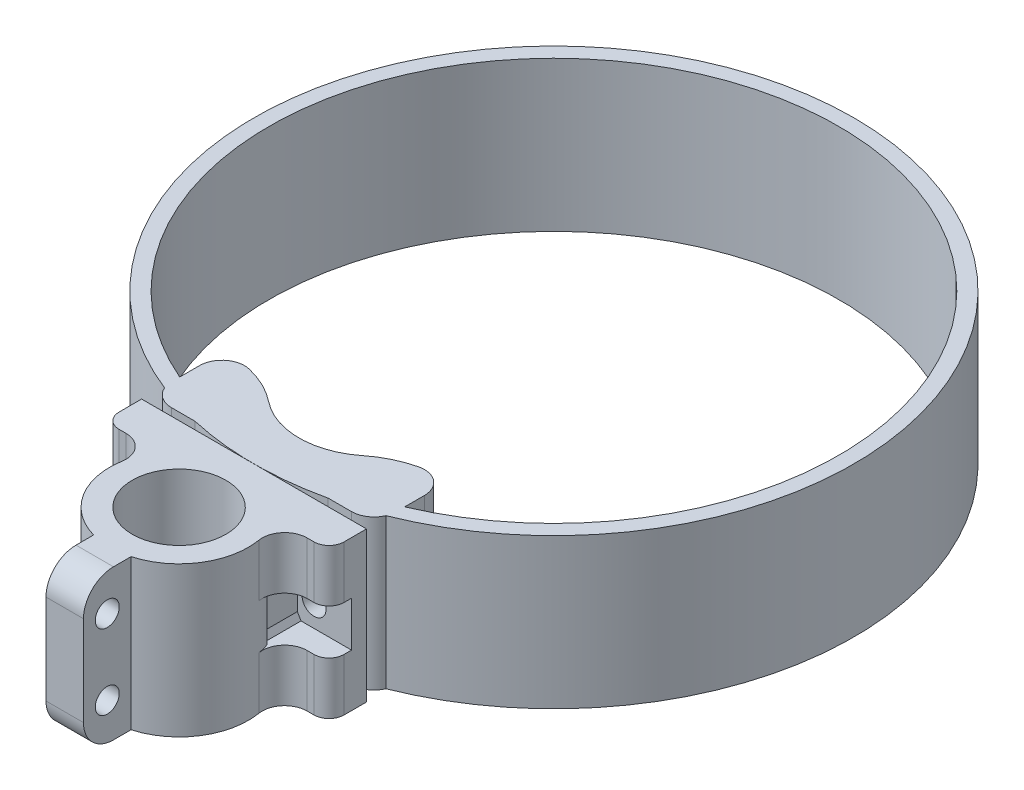
SolidWorks part; units mm, degrees
ref_plane "前视基准面" through (0, 0, 0) normal (0, 0, 1) x (1, 0, 0)
ref_plane "上视基准面" through (0, 0, 0) normal (0, 1, 0) x (1, 0, 0)
ref_plane "右视基准面" through (0, 0, 0) normal (1, 0, 0) x (0, 0, -1)
sketch "草图1" plane through (0, 0, 0) normal (0, 1, 0) x (1, 0, 0)
  circle A0 centre (0, 0) radius 6.25
  circle A1 centre (0, 0) radius 9.25
  dimension "D1" = 12.5
  dimension "D2" = 3
extrude "凸台-拉伸1" add sketch "草图1" along normal blind 20
sketch "草图3" plane through (0, 0, 0) normal (0, -1, 0) x (1, 0, 0)
  line L0 (0, 18.7983) -> (0, -20.8781) construction
  line L1 (-15, -10) -> (15, -10)
  line L2 (15, -10) -> (15, -5)
  line L3 (15, -5) -> (3.75, -5)
  line L4 (-15, -10) -> (-15, -5)
  line L5 (0, -5) -> (-3.75, -5) construction
  line L6 (-3.75, -5) -> (-15, -5)
  line L7 (3.75, -5) -> (0, -5) construction
  circle A0 centre (0, 0) radius 6.25 construction
  arc A1 (-3.75, -5) -> (3.75, -5) centre (0, 0) ccw
  arc A2 (0, 6.25) -> (-3.75, -5) centre (0, 0) ccw construction
  arc A3 (3.75, -5) -> (0, 6.25) centre (0, 0) ccw construction
  point P3 (0, -5)
  point P9 (0, -10)
  dimension "D1" = 30
  dimension "D2" = 5
  dimension "D3" = 10
extrude "凸台-拉伸2" add sketch "草图3" against normal up to surface (20 mm away) up to face at (0, 20, 9.25)
sketch "草图4" plane through (0, 0, -10) normal (0, 0, -1) x (-1, 0, 0)
  line L0 (0, 35.3363) -> (0, -16.1213) construction
  line L1 (-15, 10) -> (15, 10) construction
  line L2 (-15, 20) -> (-15, 0) construction
  line L3 (15, 20) -> (15, 0) construction
  circle A0 centre (-10, 10) radius 1.6
  circle A1 centre (10, 10) radius 1.6
  dimension "D1" = 3.2
  dimension "D2" = 20
extrude "切除-拉伸1" cut sketch "草图4" against normal up to next
ref_plane "基准面1" through (0, 0, 20) normal (0, 0, 1) x (1, 0, 0)
sketch "草图6" plane through (0, 0, 20) normal (0, 0, 1) x (1, 0, 0)
  line L0 (0, 0) -> (0, 19.0192) construction
  line L1 (-10, 13.4641) -> (-13, 11.7321)
  line L2 (-13, 11.7321) -> (-13, 8.2679)
  line L3 (-13, 8.2679) -> (-10, 6.5359)
  line L4 (-10, 6.5359) -> (-7, 8.2679)
  line L5 (-7, 8.2679) -> (-7, 11.7321)
  line L6 (-7, 11.7321) -> (-10, 13.4641)
  line L7 (7, 11.7321) -> (10, 13.4641)
  line L8 (7, 8.2679) -> (7, 11.7321)
  line L9 (10, 6.5359) -> (7, 8.2679)
  line L10 (13, 8.2679) -> (10, 6.5359)
  line L11 (13, 11.7321) -> (13, 8.2679)
  line L12 (10, 13.4641) -> (13, 11.7321)
  circle A2 centre (-10, 10) radius 3 construction
  dimension "D1" = 6
sketch "草图7" plane through (0, 0, -5) normal (0, 0, 1) x (1, 0, 0)
  line L0 (-11.7321, 13) -> (-15, 13)
  line L1 (-6.5359, 10) -> (-8.2679, 13)
  line L2 (-8.2679, 13) -> (-11.7321, 13)
  line L3 (-11.7321, 13) -> (-13.4641, 10)
  line L4 (-13.4641, 10) -> (-11.7321, 7)
  line L5 (-11.7321, 7) -> (-8.2679, 7)
  line L6 (-8.2679, 7) -> (-6.5359, 10)
  line L7 (-15, 20) -> (-15, 0) construction
  line L8 (-15, 13) -> (-15, 7)
  line L9 (-15, 7) -> (-11.7321, 7)
  line L10 (0, -2.9099) -> (0, 23.8281) construction
  line L11 (11.7321, 13) -> (15, 13)
  line L12 (15, 7) -> (11.7321, 7)
  line L13 (15, 13) -> (15, 7)
  line L14 (8.2679, 7) -> (6.5359, 10)
  line L15 (11.7321, 7) -> (8.2679, 7)
  line L16 (13.4641, 10) -> (11.7321, 7)
  line L17 (11.7321, 13) -> (13.4641, 10)
  line L18 (8.2679, 13) -> (11.7321, 13)
  line L19 (6.5359, 10) -> (8.2679, 13)
  circle A0 centre (-10, 10) radius 3 construction
  dimension "D1" = 6
extrude "切除-拉伸5" cut sketch "草图7" against normal blind 3
sketch "草图9" plane through (0, 0, 0) normal (0, 1, 0) x (1, 0, 0)
  line L0 (0, 2.9381) -> (0, -13.8692) construction
  line L2 (-2.5, -15.25) -> (2.5, -15.25)
  line L3 (-2.5, -15.25) -> (-2.5, -8.25)
  line L4 (-2.5, -8.25) -> (2.5, -8.25)
  line L5 (2.5, -15.25) -> (2.5, -8.25)
  line L6 (-2.5, -15.25) -> (2.5, -8.25) construction
  line L7 (-2.5, -8.25) -> (2.5, -15.25) construction
  arc A2 (-7.7822, 5) -> (7.7822, 5) centre (0, 0) ccw construction
  point P3 (0, -11.75)
  dimension "D3" = 6
  dimension "D1" = 7
  dimension "D2" = 5
extrude "凸台-拉伸3" add sketch "草图9" along normal up to surface (20 mm away) up to face at (0, 20, -4.2917)
sketch "草图10" plane through (-2.5, 0, 0) normal (-1, 0, 0) x (0, 0, 1)
  line L0 (12.0779, 20) -> (12.0779, 0) construction
  line L1 (8.9058, 20) -> (15.25, 20) construction
  line L2 (8.9058, 0) -> (15.25, 0) construction
  line L3 (15.25, 10) -> (5.2269, 10) construction
  line L4 (15.25, 20) -> (15.25, 0) construction
  circle A0 centre (12.0779, 15) radius 1.6
  circle A1 centre (12.0779, 5) radius 1.6
  dimension "D1" = 3.2
  dimension "D2" = 10
extrude "切除-拉伸7" cut sketch "草图10" against normal up to next
fillet "圆角1" radius 4 2 edges at (0, 0, 15.25) (0, 20, 15.25)
sketch "草图11" plane through (0, 0, 0) normal (0, -1, 0) x (1, 0, 0)
  line L0 (15, -5) -> (7.7822, -5) construction
  line L1 (12.0856, -5) -> (7.7822, -5)
  line L2 (0, 4.128) -> (0, -10.8528) construction
  line L3 (-12.0856, -5) -> (-7.7822, -5)
  arc A0 (7.7822, -5) -> (2.5, 8.9058) centre (0, 0) ccw construction
  arc A1 (7.7822, -5) -> (9.1259, -1.5102) centre (0, 0) ccw
  arc A2 (9.1259, -1.5102) -> (12.0856, -5) centre (12.0856, -2) ccw
  arc A3 (-9.1259, -1.5102) -> (-12.0856, -5) centre (-12.0856, -2) cw
  arc A4 (-7.7822, -5) -> (-9.1259, -1.5102) centre (0, 0) cw
  dimension "D1" = 6
extrude "凸台-拉伸4" add sketch "草图11" against normal blind 7
ref_plane "基准面2" through (0, 10, 0) normal (0, 1, 0) x (1, 0, 0)
mirror "镜向2" about plane through (0, 10, 0) normal (0, 1, 0) of "凸台-拉伸4"
sketch "草图16" plane through (0, 0, -8) normal (0, 0, 1) x (1, 0, 0)
  line L0 (0, 23.76) -> (0, -2.208) construction
  line L6 (-15, 7) -> (-8.2679, 7)
  line L7 (8.2679, 7) -> (15, 7)
  line L8 (15, 7) -> (15, 13)
  line L9 (15, 13) -> (8.2679, 13)
  line L10 (8.2679, 13) -> (7.7822, 12.1586)
  line L11 (7.7822, 12.1586) -> (7.7822, 7.8414)
  line L12 (7.7822, 7.8414) -> (8.2679, 7)
  line L13 (8.2679, 7) -> (15, 7)
  line L14 (15, 7) -> (15, 13)
  line L15 (15, 13) -> (8.2679, 13)
  line L16 (8.2679, 13) -> (7.7822, 12.1586)
  line L17 (7.7822, 12.1586) -> (7.7822, 7.8414)
  line L18 (7.7822, 7.8414) -> (8.2679, 7)
  line L19 (-8.2679, 7) -> (-6.5359, 10)
  line L20 (-6.5359, 10) -> (-8.2679, 13)
  line L21 (-8.2679, 13) -> (-15, 13)
  line L22 (-15, 13) -> (-15, 7)
  line L23 (-15, 7) -> (-8.2679, 7)
  line L24 (-8.2679, 7) -> (-6.5359, 10)
  line L25 (-6.5359, 10) -> (-8.2679, 13)
  line L26 (-8.2679, 13) -> (-15, 13)
  line L27 (-15, 13) -> (-15, 7)
  dimension "D1" = 0
  dimension "D2" = 0
extrude "切除-拉伸8" cut sketch "草图16" along normal blind 5
sketch "草图17" plane through (0, 0, -5) normal (0, 0, 1) x (1, 0, 0)
  line L3 (-8.2679, 7) -> (-7.7822, 7)
  line L4 (-7.7822, 7) -> (-7.7822, 7.8414)
  line L5 (-7.7822, 7.8414) -> (-8.2679, 7)
  line L6 (-8.2679, 7) -> (-7.7822, 7)
  line L7 (-7.7822, 7) -> (-7.7822, 7.8414)
  line L8 (-7.7822, 7.8414) -> (-8.2679, 7)
  line L9 (-7.7822, 13) -> (-8.2679, 13)
  line L10 (-8.2679, 13) -> (-7.7822, 12.1586)
  line L11 (-7.7822, 12.1586) -> (-7.7822, 13)
  line L12 (-7.7822, 13) -> (-8.2679, 13)
  line L13 (-8.2679, 13) -> (-7.7822, 12.1586)
  line L14 (-7.7822, 12.1586) -> (-7.7822, 13)
  line L15 (7.7822, 12.1586) -> (8.2679, 13)
  line L16 (8.2679, 13) -> (7.7822, 13)
  line L17 (7.7822, 13) -> (7.7822, 12.1586)
  line L18 (7.7822, 12.1586) -> (8.2679, 13)
  line L19 (8.2679, 13) -> (7.7822, 13)
  line L20 (7.7822, 13) -> (7.7822, 12.1586)
  line L21 (7.7822, 7.8414) -> (7.7822, 7)
  line L22 (7.7822, 7) -> (8.2679, 7)
  line L23 (8.2679, 7) -> (7.7822, 7.8414)
  line L24 (7.7822, 7.8414) -> (7.7822, 7)
  line L25 (7.7822, 7) -> (8.2679, 7)
  line L26 (8.2679, 7) -> (7.7822, 7.8414)
  dimension "D1" = 0
  dimension "D2" = 0
  dimension "D3" = 0
  dimension "D4" = 0
extrude "凸台-拉伸5" add sketch "草图17" along normal blind 1
split "分割1" trim tools "右视基准面" bodies to split 122 resulting bodies 119 120
sketch "草图18" plane through (0, 0, 0) normal (0, -1, 0) x (1, 0, 0)
  line L0 (0, 0) -> (0, -38.3211) construction
  line L1 (-15, -21) -> (-15, -11)
  line L2 (-15, -21) -> (-8.6603, -21)
  line L3 (-15, -11) -> (15, -11)
  line L4 (15, -21) -> (15, -11)
  line L5 (15, -21) -> (8.6603, -21)
  line L6 (0, -10) -> (15, -10) construction
  line L7 (-15, -5) -> (-15, -10) construction
  circle A0 centre (0, -26) radius 10
  dimension "D1" = 20
  dimension "D2" = 16
  dimension "D3" = 1
  dimension "D4" = 10
extrude "凸台-拉伸6" add sketch "草图18" against normal up to surface (20 mm away) separate body contours L0 L3 L1 L2 A0 | L3 L0 A0 L5 L4 up to face at (6.3645, 20, 0.0477)
fillet "圆角7" radius 13 2 edges at (-8.6603, 10, -21) (8.6603, 10, -21)
sketch "草图19" plane through (0, 0, -21) normal (0, 0, -1) x (-1, 0, 0)
  circle A0 centre (10, 10) radius 1.6 construction
  circle A1 centre (-10, 10) radius 1.6 construction
  circle A2 centre (10, 10) radius 1.6
  circle A3 centre (-10, 10) radius 1.6
extrude "切除-拉伸9" cut sketch "草图19" against normal up to next
sketch "草图20" plane through (0, 0, -21) normal (0, 0, -1) x (-1, 0, 0)
  circle A0 centre (10, 10) radius 3
  circle A1 centre (-10, 10) radius 3
  dimension "D1" = 6
  dimension "D2" = 6
extrude "切除-拉伸10" cut sketch "草图20" against normal offset from surface (6 mm away) 4 up to face at (-11.6, 10, -11)
fillet "圆角4" radius 2 2 edges at (15, 3.5, -5) (15, 16.5, -5)
fillet "圆角5" radius 2 2 edges at (-15, 3.5, -5) (-15, 16.5, -5)
fillet "圆角6" radius 3 4 edges at (-15, 10, -11) (15, 10, -11) (-15, 10, -21) (15, 10, -21)
sketch "草图21" plane through (0, 20, 0) normal (0, 1, 0) x (1, 0, 0)
  line L0 (0, 146.34) -> (0, -124.8086) construction
  line L1 (0, 10) -> (15, 10) construction
  circle A0 centre (0, 50) radius 40
  circle A1 centre (0, 50) radius 38
  dimension "D1" = 80
  dimension "D2" = 2
extrude "凸台-拉伸7" add sketch "草图21" against normal up to surface (20 mm away)
